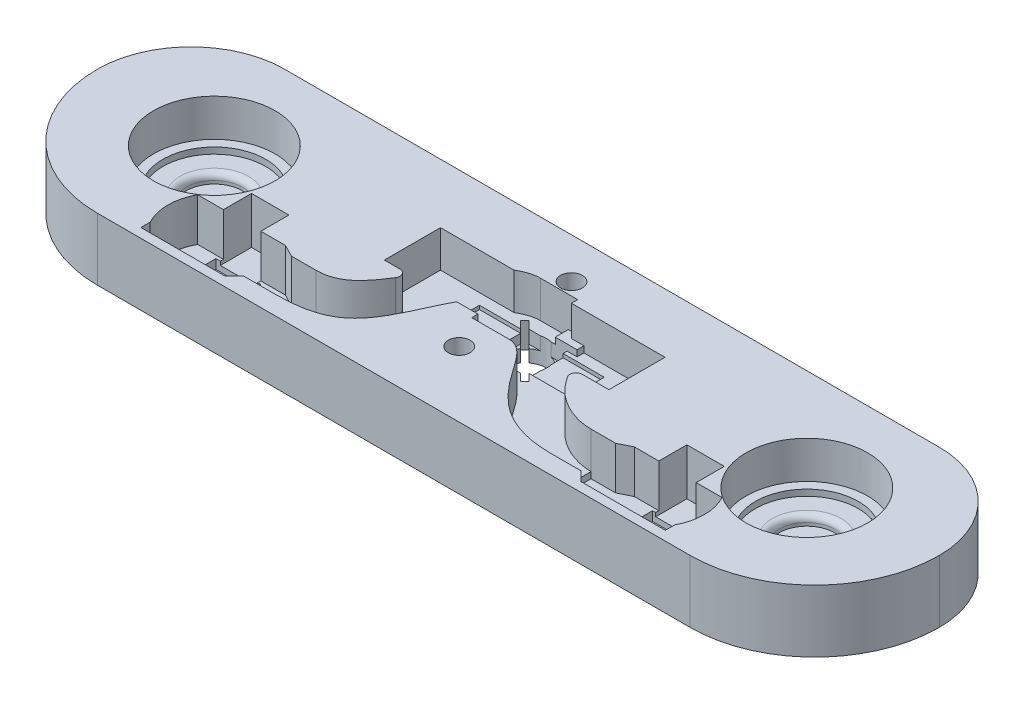
SolidWorks part; units mm, degrees
material "ABS"
ref_plane "Front Plane" through (0, 0, 0) normal (0, 0, 1) x (1, 0, 0)
ref_plane "Top Plane" through (0, 0, 0) normal (0, 1, 0) x (1, 0, 0)
ref_plane "Right Plane" through (0, 0, 0) normal (1, 0, 0) x (0, 0, -1)
sketch "Sketch1" plane through (0, 0, 0) normal (0, 1, 0) x (1, 0, 0)
  line L1 (-47.7502, 9.3769) -> (87.2498, 9.3769)
  line L2 (-47.7502, 9.3769) -> (-47.7502, -25.6231)
  line L3 (-47.7502, -25.6231) -> (87.2498, -25.6231)
  line L4 (87.2498, 9.3769) -> (87.2498, -25.6231)
  dimension "D1" = 35
  dimension "D2" = 135
extrude "Boss-Extrude1" add sketch "Sketch1" along normal blind 10
fillet "Fillet1" radius 20 2 edges at (-47.7502, 5, 25.6231) (87.2498, 5, 25.6231)
sketch "Sketch3" plane through (0, 10, 0) normal (0, 1, 0) x (1, 0, 0)
  line L1 (-47.7502, 9.3769) -> (-47.7502, -5.6231) construction
  line L2 (87.2498, 9.3769) -> (-47.7502, 9.3769) construction
  line L3 (19.7498, 5.0244) -> (19.7498, 27.1098) construction
  circle A0 centre (-27.7502, -6.8863) radius 9.75
  circle A1 centre (67.2498, -6.8863) radius 9.75
  dimension "D1" = 19.5
  dimension "D2" = 20
  dimension "D3" = 16.2632
  dimension "D4" = 67.5
sketch "Sketch5" plane through (0, 10, 0) normal (0, 1, 0) x (1, 0, 0)
  line L0 (87.2498, -5.6231) -> (87.2498, 9.3769) construction
  line L1 (87.2498, 9.3769) -> (-47.7502, 9.3769) construction
  circle A0 centre (19.7498, 2.8769) radius 1.75
  circle A1 centre (19.7498, -15.1231) radius 1.75
  dimension "D1" = 3.5
  dimension "D2" = 67.5
  dimension "D3" = 6.5
  dimension "D4" = 18
extrude "Cut-Extrude3" cut sketch "Sketch5" against normal up to next
sketch "Sketch6" plane through (0, 0, 0) normal (0, -1, 0) x (1, 0, 0)
  circle A0 centre (19.7498, 15.1231) radius 3.1
  circle A1 centre (19.7498, -2.8769) radius 3.1
  dimension "D1" = 6.2
  dimension "D2" = 6.2
extrude "Cut-Extrude4" cut sketch "Sketch6" against normal blind 4
fillet "Fillet2" radius 15 2 edges at (-47.7502, 5, -9.3769) (87.2498, 5, -9.3769)
extrude "Cut-Extrude5" cut sketch "Sketch3" against normal blind 7
sketch "Sketch9" plane through (0, 3, 0) normal (0, 1, 0) x (1, 0, 0)
  circle A0 centre (-27.7502, -6.8863) radius 8.25
  circle A1 centre (-27.7502, -6.8863) radius 9.75 construction
  circle A2 centre (-27.7502, -6.8863) radius 9.75
  circle A3 centre (67.2498, -6.8863) radius 8.25
  circle A4 centre (67.2498, -6.8863) radius 9.75 construction
  circle A5 centre (67.2498, -6.8863) radius 9.75
  dimension "D1" = 16.5
  dimension "D2" = 16.5
extrude "Boss-Extrude2" add sketch "Sketch9" along normal blind 1
sketch "Sketch10" plane through (0, 3, 0) normal (0, 1, 0) x (1, 0, 0)
  circle A0 centre (-27.7502, -6.8863) radius 4.5
  circle A1 centre (67.2498, -6.8863) radius 4.5
  dimension "D1" = 9
  dimension "D2" = 9
extrude "Cut-Extrude6" cut sketch "Sketch10" against normal blind 1.5
fillet "Fillet3" radius 1 2 edges at (67.2498, 3, 11.3863) (-27.7502, 3, 11.3863)
sketch "Sketch7" plane through (0, 10, 0) normal (0, 1, 0) x (1, 0, 0)
  circle A0 centre (-15.2502, -18.6231) radius 2.5
  circle A1 centre (54.7498, -18.6231) radius 2.5
  circle A2 centre (19.7498, 2.8769) radius 1.75 construction
  circle A3 centre (19.7498, -15.1231) radius 1.75 construction
  dimension "D3" = 5
  dimension "D4" = 5
  dimension "D1" = 70
  dimension "D2" = 35
  dimension "D5" = 3.5
extrude "Cut-Extrude7" cut sketch "Sketch7" against normal up to next
sketch "Sketch11" plane through (0, 10, 0) normal (0, 1, 0) x (1, 0, 0)
  line L0 (19.7498, 2.8769) -> (19.7498, -15.1231) construction
  line L1 (-18.8502, -15.5231) -> (-11.6502, -15.5231)
  line L2 (-18.8502, -15.5231) -> (-18.8502, -21.7231)
  line L3 (-18.8502, -21.7231) -> (-11.6502, -21.7231)
  line L4 (-11.6502, -15.5231) -> (-11.6502, -21.7231)
  line L5 (58.3498, -21.7231) -> (51.1498, -21.7231)
  line L6 (58.3498, -15.5231) -> (58.3498, -21.7231)
  line L7 (58.3498, -15.5231) -> (51.1498, -15.5231)
  line L8 (51.1498, -15.5231) -> (51.1498, -21.7231)
  circle A0 centre (-15.2502, -18.6231) radius 2.5 construction
  dimension "D1" = 7.2
  dimension "D2" = 6.2
  dimension "D3" = 3.6
  dimension "D4" = 3.1
extrude "Cut-Extrude8" cut sketch "Sketch11" against normal offset from surface (8.4 mm away) 1.6 up to face at (-15.2502, 0, 21.1231)
sketch "Sketch12" plane through (0, 10, 0) normal (0, 1, 0) x (1, 0, 0)
  line L1 (-2.2901, -16.0231) -> (-2.2901, -22.6231)
  line L4 (-2.2901, -22.6231) -> (-22.2901, -22.6231)
  line L6 (-22.2901, -15.0231) -> (-8.2263, -15.0231)
  line L7 (19.7498, 2.8769) -> (19.7498, -15.1231) construction
  line L13 (-15.2502, -18.6231) -> (-15.2502, -20.1787) construction
  line L14 (-8.2263, -15.0231) -> (-6.2263, -16.0231)
  line L15 (-6.2263, -16.0231) -> (-2.2901, -16.0231)
  line L16 (54.7498, -18.6231) -> (54.7498, -20.1787) construction
  line L17 (45.7258, -16.0231) -> (41.7897, -16.0231)
  line L18 (47.7258, -15.0231) -> (45.7258, -16.0231)
  line L19 (61.7897, -15.0231) -> (47.7258, -15.0231)
  line L20 (41.7897, -22.6231) -> (61.7897, -22.6231)
  line L21 (41.7897, -16.0231) -> (41.7897, -22.6231)
  arc A0 (-22.2901, -15.0231) -> (-22.2901, -22.6231) centre (-15.2502, -18.8231) ccw
  circle A1 centre (-15.2502, -18.6231) radius 2.5 construction
  arc A2 (61.7897, -15.0231) -> (61.7897, -22.6231) centre (54.7498, -18.8231) cw
  dimension "D2" = 7.6
  dimension "D3" = 20
  dimension "D4" = 8
  dimension "D1" = 4
  dimension "D5" = 3.9362
  dimension "D6" = 2
  dimension "D7" = 1
extrude "Cut-Extrude9" cut sketch "Sketch12" against normal offset from surface (6.9 mm away) 1.5 up to face at (-15.2502, 1.6, 18.6231)
sketch "Sketch13" plane through (0, 10, 0) normal (0, 1, 0) x (1, 0, 0)
  line L2 (16.7498, -6.1231) -> (16.7498, -10.1231)
  line L3 (16.7498, -10.1231) -> (22.7498, -10.1231)
  line L4 (16.7498, 0.8769) -> (22.7498, 0.8769)
  line L5 (22.7498, 0.8769) -> (22.7498, -3.1231)
  line L8 (-2.2901, -16.0231) -> (-2.2901, -22.6231)
  line L9 (41.7897, -16.0231) -> (41.7897, -22.6231)
  line L10 (-2.2901, -22.6231) -> (-2.2901, -16.0231) construction
  circle A0 centre (19.7498, 2.8769) radius 1.75 construction
  circle A1 centre (19.7498, -15.1231) radius 1.75 construction
  spline S0 degree 3 poles (-2.2901, -16.0231) (1.0307, -16.0231) (5.021, -11.5533) (8.4417, -4.0824) (13.9946, 0.8769) (16.7498, 0.8769) knots 0 0 0 0 0.303661 0.653033 1 1 1 1
  spline S1 degree 3 poles (-2.2901, -22.6231) (1.4581, -22.6231) (7.0853, -21.4671) (11.3493, -13.8491) (14.3598, -6.1231) (16.7498, -6.1231) knots 0 0 0 0 0.342743 0.656632 1 1 1 1
  spline S2 degree 3 poles (22.7498, -10.1231) (24.722, -10.1231) (28.164, -15.6332) (33.1217, -21.3266) (39.0959, -22.6231) (41.7897, -22.6231) knots 0 0 0 0 0.26721 0.665148 1 1 1 1
  spline S3 degree 3 poles (22.7498, -3.1231) (25.4044, -3.1231) (30.64, -6.4865) (33.8265, -13.6596) (39.2076, -16.0231) (41.7897, -16.0231) knots 0 0 0 0 0.352459 0.667621 1 1 1 1
  point P2 (-2.2901, -16.0231)
  point P13 (-2.2901, -22.6231)
  point P16 (4.3619, -11.7778)
  point P19 (9.2482, -4.1256)
  point P22 (0, 0)
  point P24 (30.0661, -7.0717)
  point P25 (41.7897, -22.6231)
  point P27 (41.7897, -16.0231)
  point P29 (0, 0)
  point P31 (34.5575, -12.9957)
  point P33 (41.7498, -15.0231)
  point P34 (34.1249, -20.8378)
  point P35 (6.5622, -20.3684)
  dimension "D4" = 2
  dimension "D6" = 3
  dimension "D1" = 7
  dimension "D2" = 7
  dimension "D3" = 4
  dimension "D5" = 6
extrude "Cut-Extrude10" cut sketch "Sketch13" against normal offset from surface (5.9 mm away) 1 up to face at (-10.7622, 3.1, 17.8897)
sketch "Sketch14" plane through (0, 0, 0) normal (0, -1, 0) x (1, 0, 0)
  line L0 (19.7498, 15.1231) -> (19.7498, -2.8769) construction
  line L1 (72.2498, -9.3769) -> (-32.7502, -9.3769) construction
  circle A0 centre (19.7498, 4.6231) radius 3.5
  dimension "D1" = 7
  dimension "D2" = 14
extrude "Cut-Extrude11" cut sketch "Sketch14" against normal up to next
sketch "Sketch15" plane through (0, 4.1, 0) normal (0, 1, 0) x (1, 0, 0)
  line L1 (16.3498, -1.2231) -> (23.1498, -1.2231)
  line L2 (16.3498, -1.2231) -> (16.3498, -8.0231)
  line L3 (16.3498, -8.0231) -> (23.1498, -8.0231)
  line L4 (23.1498, -1.2231) -> (23.1498, -8.0231)
  circle A0 centre (19.7498, -4.6231) radius 3.5 construction
  dimension "D1" = 6.8
  dimension "D2" = 6.8
  dimension "D3" = 3.4
  dimension "D4" = 3.4
extrude "Cut-Extrude12" cut sketch "Sketch15" against normal offset from surface 2 and the other way up to next (5.9 mm away)
sketch "Sketch16" plane through (0, 10, 0) normal (0, 1, 0) x (1, 0, 0)
  line L1 (1.7498, -0.1231) -> (37.7498, -0.1231)
  line L2 (1.7498, -0.1231) -> (1.7498, -9.1231)
  line L3 (1.7498, -9.1231) -> (37.7498, -9.1231)
  line L4 (37.7498, -0.1231) -> (37.7498, -9.1231)
  circle A0 centre (19.7498, -4.6231) radius 3.5 construction
  dimension "D1" = 36
  dimension "D2" = 18
  dimension "D3" = 9
  dimension "D4" = 4.5
extrude "Cut-Extrude13" cut sketch "Sketch16" against normal up to surface (5.9 mm away) up to face at (14.6852, 4.1, 5.5626)
sketch "Sketch17" plane through (0, 4.1, 0) normal (0, 1, 0) x (1, 0, 0)
  line L2 (14.3498, -8.0231) -> (18.3498, -8.0231)
  line L3 (23.1498, -8.0231) -> (20.5805, -8.0231) construction
  line L4 (18.3498, -8.0231) -> (18.3498, -10.1231)
  line L5 (16.7498, -10.1231) -> (22.7498, -10.1231) construction
  line L6 (18.3498, -10.1231) -> (16.7498, -10.1231)
  line L7 (16.7498, -10.1231) -> (16.7498, -9.1231)
  line L8 (16.7498, -9.1231) -> (14.3498, -9.1231)
  line L9 (16.7498, -9.1231) -> (13.3463, -9.1231) construction
  line L10 (14.3498, -9.1231) -> (14.3498, -8.0231)
  line L12 (21.2498, -1.2231) -> (24.7498, -1.2231)
  line L13 (16.3498, -1.2231) -> (18.9191, -1.2231) construction
  line L15 (16.3498, -1.2231) -> (16.3498, -3.7924) construction
  line L17 (24.7498, -1.2231) -> (24.7498, -0.1231)
  line L18 (37.7498, -0.1231) -> (22.7498, -0.1231) construction
  line L19 (24.7498, -0.1231) -> (22.7498, -0.1231)
  line L20 (22.7498, -0.1231) -> (22.7498, 0.8769)
  line L21 (22.7498, 0.8769) -> (21.2498, 0.8769)
  line L22 (22.7498, 0.8769) -> (16.7498, 0.8769) construction
  line L23 (21.2498, 0.8769) -> (21.2498, -1.2231)
  point P0 (14.7025, -7.8981)
  point P23 (24.6149, -1.3481)
  point P24 (25.0603, -1.3481)
  point P25 (0, 0)
  dimension "D1" = 2
  dimension "D2" = 4
  dimension "D4" = 3.5
  dimension "D5" = 2
extrude "Boss-Extrude3" add sketch "Sketch17" along normal blind 1
sketch "Sketch18" plane through (0, 10, 0) normal (0, 1, 0) x (1, 0, 0)
  line L1 (-18.1502, -15.5231) -> (-12.1502, -15.5231)
  line L2 (-18.1502, -15.5231) -> (-18.1502, -10.5231)
  line L3 (-18.1502, -10.5231) -> (-12.1502, -10.5231)
  line L4 (-12.1502, -15.5231) -> (-12.1502, -10.5231)
  line L7 (-11.6502, -15.5231) -> (-11.6502, -21.7231) construction
  line L8 (-18.8502, -15.5231) -> (-11.6502, -15.5231) construction
  line L9 (19.7498, 2.8769) -> (19.7498, -15.1231) construction
  line L10 (51.6498, -15.5231) -> (51.6498, -10.5231)
  line L11 (57.6498, -10.5231) -> (51.6498, -10.5231)
  line L12 (57.6498, -15.5231) -> (57.6498, -10.5231)
  line L13 (57.6498, -15.5231) -> (51.6498, -15.5231)
  dimension "D1" = 6
  dimension "D2" = 5
  dimension "D3" = 0.5
extrude "Cut-Extrude14" cut sketch "Sketch18" against normal blind 7.5
sketch "Sketch19" plane through (0, 10, 0) normal (0, 1, 0) x (1, 0, 0)
  line L0 (19.7498, 2.8769) -> (19.7498, -15.1231) construction
  line L1 (-22.2901, -22.6231) -> (-9.2901, -22.6231)
  line L2 (-22.2901, -22.6231) -> (-22.2901, -24.1231)
  line L3 (-22.2901, -24.1231) -> (-9.2901, -24.1231)
  line L4 (-9.2901, -22.6231) -> (-9.2901, -24.1231)
  line L5 (48.7897, -22.6231) -> (48.7897, -24.1231)
  line L6 (61.7897, -24.1231) -> (48.7897, -24.1231)
  line L7 (61.7897, -22.6231) -> (61.7897, -24.1231)
  line L8 (61.7897, -22.6231) -> (48.7897, -22.6231)
  point P5 (19.7498, -15.1231)
  point P15 (-9.1179, -22.6231)
  dimension "D1" = 1.5
  dimension "D2" = 13
extrude "Cut-Extrude15" cut sketch "Sketch19" against normal up to surface (6.9 mm away) up to face at (-13.2982, 3.1, 17.3516)
chamfer "Chamfer1" distance 2 angle 45 2 edges at (48.7897, 6.55, 22.6231) (-9.2901, 6.55, 22.6231)
fillet "Fillet4" radius 1 2 edges at (31.6102, 7.05, 9.1231) (6.0166, 7.05, 9.1231)
sketch "Sketch20" plane through (0, 3.1, 0) normal (0, 1, 0) x (1, 0, 0)
  line L0 (-20.7502, -18.6231) -> (-9.7502, -18.6231) construction
  line L1 (19.7498, 2.8769) -> (19.7498, -14.8566) construction
  line L2 (60.2498, -18.6231) -> (49.2498, -18.6231) construction
  circle A0 centre (-20.7502, -18.6231) radius 0.7
  circle A1 centre (-15.2502, -18.6231) radius 2.5 construction
  circle A2 centre (-9.7502, -18.6231) radius 0.7
  circle A3 centre (49.2498, -18.6231) radius 0.7
  circle A4 centre (60.2498, -18.6231) radius 0.7
  dimension "D1" = 5.5
  dimension "D2" = 5.5
  dimension "D3" = 1.4
  dimension "D4" = 1.4
  dimension "D5" = 0
extrude "Cut-Extrude16" cut sketch "Sketch20" against normal up to next
sketch "Sketch21" plane through (0, 4.1, 0) normal (0, 1, 0) x (1, 0, 0)
  line L0 (15.1536, -0.734) -> (23.6389, -9.2193)
  line L1 (23.6389, -9.2193) -> (24.346, -8.5122)
  line L2 (24.346, -8.5122) -> (15.8607, -0.0269)
  line L3 (15.8607, -0.0269) -> (15.1536, -0.734)
  line L4 (19.7498, -4.6231) -> (19.7498, -15.1231) construction
  arc A0 (23.1498, -3.7924) -> (20.5805, -1.2231) centre (19.7498, -4.6231) ccw construction
  point P7 (15.2631, -0.6245)
  dimension "D1" = 12
  dimension "D2" = 6
  dimension "D3" = 1
  dimension "D4" = 135
  dimension "D5" = 0.5
extrude "Cut-Extrude17" cut sketch "Sketch21" against normal up to next
sketch "Sketch22" plane through (0, 4.1, 0) normal (0, 1, 0) x (1, 0, 0)
  line L1 (9.7498, -1.8731) -> (29.7498, -1.8731)
  line L2 (9.7498, -1.8731) -> (9.7498, -7.3731)
  line L3 (9.7498, -7.3731) -> (29.7498, -7.3731)
  line L4 (29.7498, -1.8731) -> (29.7498, -7.3731)
  arc A0 (20.5805, -1.2231) -> (18.9191, -1.2231) centre (19.7498, -4.6231) ccw construction
  arc A1 (16.9468, -2.5271) -> (16.3498, -3.7924) centre (19.7498, -4.6231) ccw construction
  dimension "D1" = 20
  dimension "D2" = 10
  dimension "D3" = 2.75
  dimension "D4" = 5.5
extrude "Cut-Extrude18" cut sketch "Sketch22" against normal offset from surface (0.6 mm away) 1.5 up to face at (16.5275, 2, 2.7399)
equation "\"D2@Sketch7\"=\"D1@Sketch7\"/2"
equation "\"D3@Sketch7\"=\"D4@Sketch7\""
equation "\"D3@Sketch11\"=\"D1@Sketch11\"/2"
equation "\"D4@Sketch11\"=\"D2@Sketch11\"/2"
equation "\"D3@Sketch15\"=\"D1@Sketch15\"/2"
equation "\"D4@Sketch15\"=\"D1@Sketch15\"/2"
equation "\"D4@Sketch16\"=\"D3@Sketch16\"/2"
equation "\"D2@Sketch21\"=\"D1@Sketch21\"/2"
equation "\"D5@Sketch21\"=\"D3@Sketch21\"/2"
equation "\"D3@Sketch22\"=\"D4@Sketch22\"/2"
